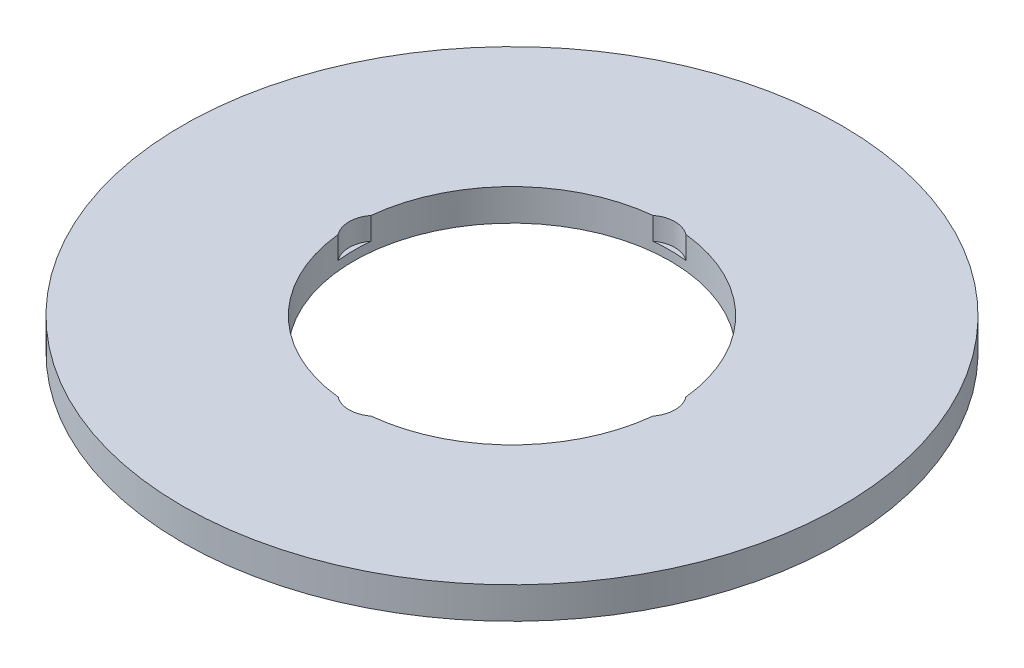
SolidWorks part; units mm, degrees
ref_plane "Front Plane" through (0, 0, 0) normal (0, 0, 1) x (1, 0, 0)
ref_plane "Top Plane" through (0, 0, 0) normal (0, 1, 0) x (1, 0, 0)
ref_plane "Right Plane" through (0, 0, 0) normal (1, 0, 0) x (0, 0, -1)
sketch "Sketch1" plane through (0, 0, 0) normal (0, 1, 0) x (1, 0, 0)
  circle A0 centre (0, 0) radius 62.5
  dimension "FLANGE_OD" = 125
extrude "Boss-Extrude1" add sketch "Sketch1" along normal blind 6
sketch "Sketch2" plane through (0, 0, 0) normal (0, 1, 0) x (1, 0, 0)
  circle A0 centre (0, 0) radius 30
  dimension "BORE_D" = 60
extrude "Cut-Extrude1" cut sketch "Sketch2" along normal through all
sketch "Sketch3" plane through (0, 6, 0) normal (0, 1, 0) x (1, 0, 0)
  circle A0 centre (0, 0) radius 25.7847 construction
  circle A1 centre (-25.7847, 0) radius 5.1181
  dimension "BOLT_D" = 10.2362
  dimension "BOLT_PCD" = 51.5694
extrude "Cut-Extrude2" cut sketch "Sketch3" against normal blind 4.2506
pattern_circular "CirPattern1" count 4 over 360 about axis through (0, 0, 0) along (0, 1, 0) of "Cut-Extrude2"
